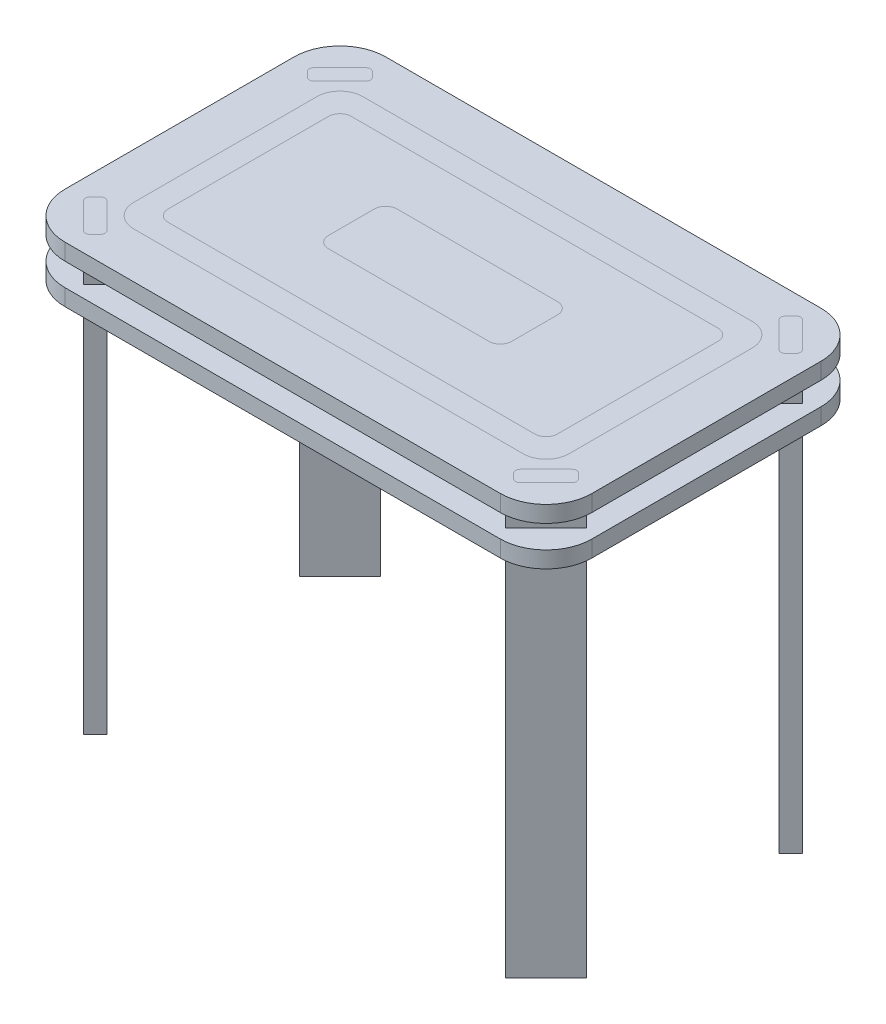
SolidWorks part; units mm, degrees
ref_plane "Front Plane" through (0, 0, 0) normal (0, 0, 1) x (1, 0, 0)
ref_plane "Top Plane" through (0, 0, 0) normal (0, 1, 0) x (1, 0, 0)
ref_plane "Right Plane" through (0, 0, 0) normal (1, 0, 0) x (0, 0, -1)
sketch "Sketch1" plane through (0, 0, 0) normal (0, 1, 0) x (1, 0, 0)
  line L0 (76.2, 50.8) -> (508, 50.8)
  line L1 (50.8, 0) -> (533.4, 0)
  line L2 (0, 50.8) -> (0, 304.8)
  line L3 (50.8, 355.6) -> (533.4, 355.6)
  line L4 (584.2, 50.8) -> (584.2, 304.8)
  line L5 (533.4, 76.2) -> (533.4, 279.4)
  line L6 (76.2, 304.8) -> (508, 304.8)
  line L7 (50.8, 76.2) -> (50.8, 279.4)
  line L8 (50.8, 50.8) -> (533.4, 50.8) construction
  line L9 (533.4, 50.8) -> (533.4, 304.8) construction
  line L10 (50.8, 304.8) -> (533.4, 304.8) construction
  line L11 (50.8, 50.8) -> (50.8, 304.8) construction
  line L12 (88.9, 76.2) -> (495.3, 76.2)
  line L13 (508, 88.9) -> (508, 266.7)
  line L14 (88.9, 279.4) -> (495.3, 279.4)
  line L15 (76.2, 88.9) -> (76.2, 266.7)
  line L16 (21.3721, 298.3069) -> (27.097, 292.582)
  line L17 (34.2812, 292.582) -> (63.018, 321.3188)
  line L18 (63.018, 328.503) -> (57.2931, 334.2279)
  line L19 (50.1089, 334.2279) -> (21.3721, 305.4911)
  line L20 (292.1, 0) -> (292.1, 360.5975) construction
  line L21 (0, 177.8) -> (612.0306, 177.8) construction
  line L22 (562.8279, 298.3069) -> (557.103, 292.582)
  line L23 (549.9188, 292.582) -> (521.182, 321.3188)
  line L24 (534.0911, 334.2279) -> (562.8279, 305.4911)
  line L25 (521.182, 328.503) -> (526.9069, 334.2279)
  line L26 (521.182, 27.097) -> (526.9069, 21.3721)
  line L27 (534.0911, 21.3721) -> (562.8279, 50.1089)
  line L28 (549.9188, 63.018) -> (521.182, 34.2812)
  line L29 (562.8279, 57.2931) -> (557.103, 63.018)
  line L30 (50.1089, 21.3721) -> (21.3721, 50.1089)
  line L31 (63.018, 27.097) -> (57.2931, 21.3721)
  line L32 (34.2812, 63.018) -> (63.018, 34.2812)
  line L33 (21.3721, 57.2931) -> (27.097, 63.018)
  line L34 (76.2, 76.2) -> (508, 76.2) construction
  line L35 (508, 76.2) -> (508, 279.4) construction
  line L36 (76.2, 279.4) -> (508, 279.4) construction
  line L37 (76.2, 76.2) -> (76.2, 279.4) construction
  line L39 (203.2, 215.9) -> (381, 215.9)
  line L40 (190.5, 203.2) -> (190.5, 152.4)
  line L41 (203.2, 139.7) -> (381, 139.7)
  line L42 (393.7, 203.2) -> (393.7, 152.4)
  arc A0 (50.8, 0) -> (0, 50.8) centre (50.8, 50.8) cw
  arc A1 (533.4, 0) -> (584.2, 50.8) centre (533.4, 50.8) ccw
  arc A2 (533.4, 355.6) -> (584.2, 304.8) centre (533.4, 304.8) cw
  arc A3 (0, 304.8) -> (50.8, 355.6) centre (50.8, 304.8) cw
  arc A4 (508, 304.8) -> (533.4, 279.4) centre (508, 279.4) cw
  arc A5 (50.8, 279.4) -> (76.2, 304.8) centre (76.2, 279.4) cw
  arc A6 (50.8, 76.2) -> (76.2, 50.8) centre (76.2, 76.2) ccw
  arc A7 (508, 266.7) -> (495.3, 279.4) centre (495.3, 266.7) ccw
  arc A8 (508, 50.8) -> (533.4, 76.2) centre (508, 76.2) ccw
  arc A9 (533.4, 50.8) -> (533.4, 50.8) centre (533.4, 50.8) ccw construction
  arc A10 (533.4, 304.8) -> (533.4, 304.8) centre (533.4, 304.8) cw construction
  arc A11 (50.8, 304.8) -> (50.8, 304.8) centre (50.8, 304.8) cw construction
  arc A12 (50.8, 50.8) -> (50.8, 50.8) centre (50.8, 50.8) cw construction
  arc A13 (76.2, 266.7) -> (88.9, 279.4) centre (88.9, 266.7) cw
  arc A14 (76.2, 88.9) -> (88.9, 76.2) centre (88.9, 88.9) ccw
  arc A15 (203.2, 215.9) -> (190.5, 203.2) centre (203.2, 203.2) ccw
  arc A16 (21.3721, 298.3069) -> (21.3721, 305.4911) centre (24.9642, 301.899) cw
  arc A17 (34.2812, 292.582) -> (27.097, 292.582) centre (30.6891, 296.1741) cw
  arc A18 (63.018, 328.503) -> (63.018, 321.3188) centre (59.4259, 324.9109) cw
  arc A19 (57.2931, 334.2279) -> (50.1089, 334.2279) centre (53.701, 330.6358) ccw
  arc A20 (549.9188, 292.582) -> (557.103, 292.582) centre (553.5109, 296.1741) ccw
  arc A21 (526.9069, 334.2279) -> (534.0911, 334.2279) centre (530.499, 330.6358) cw
  arc A22 (521.182, 328.503) -> (521.182, 321.3188) centre (524.7741, 324.9109) ccw
  arc A23 (562.8279, 298.3069) -> (562.8279, 305.4911) centre (559.2358, 301.899) ccw
  arc A24 (562.8279, 57.2931) -> (562.8279, 50.1089) centre (559.2358, 53.701) cw
  arc A25 (521.182, 27.097) -> (521.182, 34.2812) centre (524.7741, 30.6891) cw
  arc A26 (526.9069, 21.3721) -> (534.0911, 21.3721) centre (530.499, 24.9642) ccw
  arc A27 (549.9188, 63.018) -> (557.103, 63.018) centre (553.5109, 59.4259) cw
  arc A28 (57.2931, 21.3721) -> (50.1089, 21.3721) centre (53.701, 24.9642) cw
  arc A29 (63.018, 27.097) -> (63.018, 34.2812) centre (59.4259, 30.6891) ccw
  arc A30 (34.2812, 63.018) -> (27.097, 63.018) centre (30.6891, 59.4259) ccw
  arc A31 (21.3721, 57.2931) -> (21.3721, 50.1089) centre (24.9642, 53.701) ccw
  arc A32 (495.3, 76.2) -> (508, 88.9) centre (495.3, 88.9) ccw
  arc A33 (508, 76.2) -> (508, 76.2) centre (508, 76.2) ccw construction
  arc A34 (508, 279.4) -> (508, 279.4) centre (508, 279.4) cw construction
  arc A35 (76.2, 279.4) -> (76.2, 279.4) centre (76.2, 279.4) cw construction
  arc A36 (76.2, 76.2) -> (76.2, 76.2) centre (76.2, 76.2) ccw construction
  arc A37 (190.5, 152.4) -> (203.2, 139.7) centre (203.2, 152.4) ccw
  arc A38 (381, 139.7) -> (393.7, 152.4) centre (381, 152.4) ccw
  arc A39 (381, 215.9) -> (393.7, 203.2) centre (381, 203.2) cw
  point P7 (0, 0)
  point P12 (584.2, 355.6)
  point P15 (0, 355.6)
  point P62 (17.78, 301.899)
  point P65 (30.6891, 288.9899)
  point P70 (53.701, 337.82)
  point P83 (566.42, 301.899)
  point P96 (566.42, 53.701)
  point P109 (53.701, 17.78)
  point P110 (30.6891, 66.6101)
  point P127 (292.1, 215.9)
  point P128 (393.7, 177.8)
  point P131 (190.5, 215.9)
  point P136 (393.7, 139.7)
  point P139 (393.7, 215.9)
  dimension "D3" = 50.8
  dimension "D5" = 25.4
  dimension "D12" = 5.08
  dimension "D13" = 12.7
  dimension "D16" = 12.7
  dimension "D1" = 584.2
  dimension "D2" = 355.6
  dimension "D7" = 50.8
  dimension "D8" = 17.78
  dimension "D9" = 17.78
  dimension "D10" = 18.2562
  dimension "D11" = 45
  dimension "D14" = 203.2
  dimension "D15" = 76.2
  dimension "D4" = 50.8
  dimension "D6" = 25.4
extrude "Boss-Extrude3" add sketch "Sketch1" along normal blind 18.288 contours A3 L2 A0 L1 A1 L4 A2 L3 A31 L33 A30 L32 A29 L31 A28 L30 A23 L22 A20 L23 A22 L25 A21 L24 A19 L18 A18 L17 A17 L16 A16 L19 A8 L0 A6 L7 A5 L6 A4 L5 L28 A27 L29 A24 L27 A26 | L12 A32 L13 A7 L14 A13 L15 A14 L39 A39 L42 A38 L41 A37 L40 A15 region at (19.715, 0, -19.715) region at (83.2942, 0, -83.2942)
extrude "Boss-Extrude4" add sketch "Sketch1<6>" along normal blind 18.288 separate body contours L0 A8 L5 A4 L6 A5 L7 A6 A32 L12 A14 L15 A13 L14 A7 L13 | A39 L39 A15 L40 A37 L41 A38 L42 region at (62.0958, 0, -62.0958) region at (292.1, 0, -177.8)
sketch "Sketch1<6>" plane through (0, 0, 0) normal (0, 1, 0) x (1, 0, 0) same geometry as "Sketch1"
extrude "Boss-Extrude5" add sketch "Sketch1<7>" along normal blind 18.288 separate body contours L18 A19 L19 A16 L16 A17 L17 A18 | A27 L28 A25 L26 A26 L27 A24 L29 | L22 A23 L24 A21 L25 A22 L23 A20 | L32 A29 L31 A28 L30 A31 L33 A30 region at (42.1951, 0, -313.4049) region at (542.0049, 0, -313.4049) region at (542.0049, 0, -42.1951)
sketch "Sketch1<7>" plane through (0, 0, 0) normal (0, 1, 0) x (1, 0, 0) same geometry as "Sketch1"
sketch "Sketch5" plane through (0, 0, 0) normal (0, -1, 0) x (1, 0, 0)
  line L0 (13.2899, -58.1912) -> (58.1912, -13.2899)
  line L1 (58.1912, -13.2899) -> (71.1003, -26.199)
  line L2 (71.1003, -26.199) -> (26.199, -71.1003)
  line L3 (26.199, -71.1003) -> (13.2899, -58.1912)
  line L5 (50.1089, -21.3721) -> (21.3721, -50.1089) construction
  line L6 (35.7405, -35.7405) -> (48.6496, -48.6496) construction
  line L7 (34.2812, -63.018) -> (63.018, -34.2812) construction
  line L8 (0, -177.8) -> (584.2, -177.8) construction
  line L9 (584.2, -50.8) -> (584.2, -304.8) construction
  line L10 (292.1, 0) -> (292.1, -320.0776) construction
  line L11 (292.1, 0) -> (292.1, -360.5975) construction
  line L12 (558.001, -71.1003) -> (570.9101, -58.1912)
  line L13 (570.9101, -58.1912) -> (526.0088, -13.2899)
  line L14 (526.0088, -13.2899) -> (513.0997, -26.199)
  line L15 (513.0997, -26.199) -> (558.001, -71.1003)
  line L16 (513.0997, -329.401) -> (558.001, -284.4997)
  line L17 (570.9101, -297.4088) -> (526.0088, -342.3101)
  line L18 (558.001, -284.4997) -> (570.9101, -297.4088)
  line L19 (526.0088, -342.3101) -> (513.0997, -329.401)
  line L20 (26.199, -284.4997) -> (13.2899, -297.4088)
  line L21 (13.2899, -297.4088) -> (58.1912, -342.3101)
  line L22 (71.1003, -329.401) -> (26.199, -284.4997)
  line L23 (58.1912, -342.3101) -> (71.1003, -329.401)
  point P10 (35.7405, -35.7405)
  dimension "D1" = 63.5
extrude "Boss-Extrude6" add sketch "Sketch5" along normal blind 457.2 separate body
ref_plane "Plane1" through (0, -25.4, 0) normal (0, 1, 0) x (1, 0, 0)
sketch "Sketch6" plane through (0, -25.4, 0) normal (0, 1, 0) x (1, 0, 0)
  line L0 (26.199, 284.4997) -> (71.1003, 329.401)
  line L1 (50.8, 0) -> (533.4, 0)
  line L2 (0, 50.8) -> (0, 304.8)
  line L3 (50.8, 355.6) -> (533.4, 355.6)
  line L4 (584.2, 50.8) -> (584.2, 304.8)
  line L5 (58.1912, 342.3101) -> (13.2899, 297.4088)
  line L6 (13.2899, 297.4088) -> (26.199, 284.4997)
  line L7 (58.1912, 342.3101) -> (71.1003, 329.401)
  line L8 (526.0088, 342.3101) -> (513.0997, 329.401)
  line L9 (570.9101, 297.4088) -> (558.001, 284.4997)
  line L10 (526.0088, 342.3101) -> (570.9101, 297.4088)
  line L11 (558.001, 284.4997) -> (513.0997, 329.401)
  line L12 (558.001, 71.1003) -> (513.0997, 26.199)
  line L13 (526.0088, 13.2899) -> (570.9101, 58.1912)
  line L14 (570.9101, 58.1912) -> (558.001, 71.1003)
  line L15 (526.0088, 13.2899) -> (513.0997, 26.199)
  line L16 (58.1912, 13.2899) -> (71.1003, 26.199)
  line L17 (13.2899, 58.1912) -> (26.199, 71.1003)
  line L18 (58.1912, 13.2899) -> (13.2899, 58.1912)
  line L19 (26.199, 71.1003) -> (71.1003, 26.199)
  line L20 (292.1, 0) -> (292.1, 360.5975) construction
  line L21 (0, 177.8) -> (612.0306, 177.8) construction
  arc A0 (50.8, 0) -> (0, 50.8) centre (50.8, 50.8) cw
  arc A1 (533.4, 0) -> (584.2, 50.8) centre (533.4, 50.8) ccw
  arc A2 (533.4, 355.6) -> (584.2, 304.8) centre (533.4, 304.8) cw
  arc A3 (50.8, 355.6) -> (0, 304.8) centre (50.8, 304.8) ccw
  point P7 (0, 0)
  point P12 (584.2, 355.6)
  point P15 (0, 355.6)
  dimension "D3" = 50.8
  dimension "D1" = 584.2
  dimension "D2" = 355.6
extrude "Boss-Extrude7" add sketch "Sketch6" against normal blind 18.288
